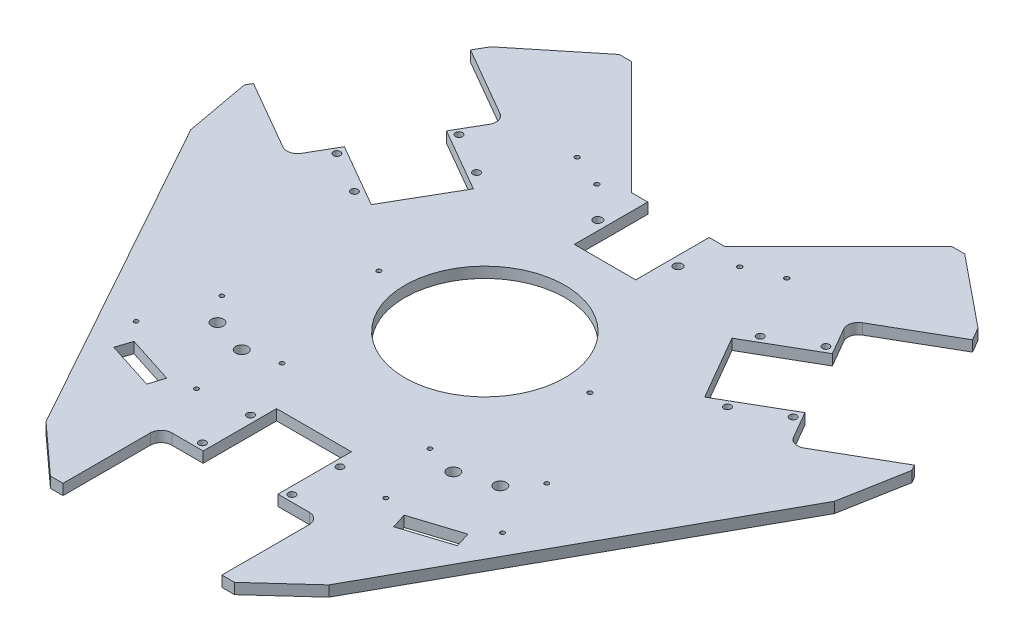
SolidWorks part; units mm, degrees
material "1060 合金"
ref_plane "前视基准面" through (0, 0, 0) normal (0, 0, 1) x (1, 0, 0)
ref_plane "上视基准面" through (0, 0, 0) normal (0, 1, 0) x (1, 0, 0)
ref_plane "右视基准面" through (0, 0, 0) normal (1, 0, 0) x (0, 0, -1)
sketch "草图1" plane through (0, 0, 0) normal (0, 1, 0) x (1, 0, 0)
  line L0 (0, 0) -> (-158.4826, 91.5) construction
  line L1 (0, 0) -> (0, 227.8132) construction
  line L2 (188.2326, 39.9715) -> (128.7326, 143.0285)
  line L3 (188.2326, 39.9715) -> (241.9262, 70.9715)
  line L4 (241.9262, 70.9715) -> (182.4262, 174.0285)
  line L5 (182.4262, 174.0285) -> (128.7326, 143.0285)
  line L6 (0, 0) -> (158.4826, 91.5) construction
  line L7 (-128.7326, 143.0285) -> (-188.2326, 39.9715)
  line L8 (-128.7326, 143.0285) -> (-182.4262, 174.0285)
  line L9 (-182.4262, 174.0285) -> (-241.9262, 70.9715)
  line L10 (-241.9262, 70.9715) -> (-188.2326, 39.9715)
  line L11 (-59.5, -183) -> (59.5, -183)
  line L12 (-59.5, -183) -> (-59.5, -245)
  line L13 (-59.5, -245) -> (59.5, -245)
  line L14 (59.5, -245) -> (59.5, -183)
  line L15 (0, 0) -> (0, -183) construction
  line L16 (-182.4262, 186.924) -> (-250, 69.8827)
  line L17 (-250, 69.8827) -> (-68.9159, -256.4698) construction
  line L18 (-68.9159, -256.4698) -> (68.9159, -256.4698)
  line L19 (250, 69.8827) -> (68.9159, -256.4698) construction
  line L20 (182.4262, 186.924) -> (250, 69.8827)
  line L21 (-129.4169, 230) -> (129.4169, 230)
  line L22 (-250, 69.8827) -> (-241.0069, 20.6982)
  line L23 (-250, -256.4698) -> (250, -256.4698) construction
  line L24 (-250, -256.4698) -> (-250, 243.5302) construction
  line L25 (-250, 243.5302) -> (250, 243.5302) construction
  line L26 (250, -256.4698) -> (250, 243.5302) construction
  line L27 (-250, -256.4698) -> (250, 243.5302) construction
  line L28 (-250, 243.5302) -> (250, -256.4698) construction
  line L29 (-241.0069, 20.6982) -> (-105.8902, -222.8112)
  line L30 (-68.9159, -256.4698) -> (-105.8902, -222.8112)
  line L31 (68.9159, -256.4698) -> (105.8902, -222.8112)
  line L32 (241.0069, 20.6982) -> (105.8902, -222.8112)
  line L33 (250, 69.8827) -> (241.0069, 20.6982)
  line L34 (-182.4262, 186.924) -> (-129.4169, 230)
  line L35 (182.4262, 186.924) -> (129.4169, 230)
  point P21 (0, 0)
  point P24 (0, 0)
  point P29 (0, -6.4698)
  dimension "D1" = 60
  dimension "D2" = 183
  dimension "D3" = 62
  dimension "D4" = 119
  dimension "D6" = 230
  dimension "D7" = 500
  dimension "D8" = 16
  dimension "D9" = 50
  dimension "D5" = 3
extrude "凸台-拉伸1" add sketch "草图1" along normal blind 8
ref_axis "基准轴1" through (0, 0, 0) along (0, 1, 0)
sketch "草图2" plane through (0, 8, 0) normal (0, 1, 0) x (1, 0, 0)
  line L0 (-124.8513, 39.7513) -> (-96.8513, 88.2487)
  line L1 (-182.4262, 174.0285) -> (-241.9262, 70.9715) construction
  line L3 (-96.8513, 88.2487) -> (-144.4826, 115.7487)
  line L4 (-212.1762, 122.5) -> (0, 0) construction
  line L6 (-144.4826, 115.7487) -> (-172.4826, 67.2513)
  line L7 (-172.4826, 67.2513) -> (-124.8513, 39.7513)
  line L8 (-188.2326, 39.9715) -> (-128.7326, 143.0285) construction
  dimension "D1" = 56
  dimension "D2" = 55
extrude "切除-拉伸1" cut sketch "草图2" against normal up to next
hole_wizard "M5 间隙孔1" positions "草图3" profile "草图4" hole size "M5" standard "GB" end condition up to next
sketch "草图3" plane through (0, 8, 0) normal (0, -1, 0) x (-1, 0, 0)
  line L0 (0, 0) -> (212.1762, 122.5) construction
  line L1 (170.9025, 59.9881) -> (139.7256, 41.9881) construction
  line L2 (170.9025, 59.9881) -> (137.4025, 118.0119) construction
  line L3 (139.7256, 41.9881) -> (106.2256, 100.0119) construction
  line L4 (137.4025, 118.0119) -> (106.2256, 100.0119) construction
  line L16 (144.4826, 115.7487) -> (128.7326, 143.0285) construction
  line L18 (182.4262, 174.0285) -> (241.9262, 70.9715) construction
  point P5 (106.2256, 100.0119)
  point P7 (137.4025, 118.0119)
  point P9 (139.7256, 41.9881)
  point P11 (170.9025, 59.9881)
  dimension "D1" = 67
  dimension "D2" = 5
  dimension "D3" = 36
sketch "草图4" plane through (-106.2256, 8, -100.0119) normal (1, 0, 0) x (0, 0, 1)
  line L0 (0, 0) -> (0, 8.001)
  line L1 (0, 8.001) -> (2.65, 8.001)
  line L2 (2.65, 8.001) -> (2.65, 0)
  line L5 (2.65, 0) -> (0, 0)
  line L11 (0, -6.35) -> (0, 107.95) construction
  dimension "通孔孔直径" = 5.3
  dimension "通孔孔深度" = 8.001
sketch "草图11" plane through (0, 8, 0) normal (0, 1, 0) x (1, 0, 0)
  line L0 (182.4262, 174.0285) -> (241.9262, 70.9715)
  line L1 (182.4262, 174.0285) -> (188.0101, 177.2524)
  line L2 (241.9262, 70.9715) -> (247.5101, 74.1953)
  line L3 (188.0101, 177.2524) -> (247.5101, 74.1953)
  line L4 (182.4262, 186.924) -> (250, 69.8827) construction
  line L5 (-59.5, -245) -> (59.5, -245)
  line L6 (-59.5, -245) -> (-59.5, -256.4698)
  line L7 (59.5, -245) -> (59.5, -256.4698)
  line L8 (-59.5, -256.4698) -> (59.5, -256.4698)
  line L9 (-68.9159, -256.4698) -> (68.9159, -256.4698) construction
  line L10 (-241.9262, 70.9715) -> (-182.4262, 174.0285)
  line L11 (-241.9262, 70.9715) -> (-247.5101, 74.1953)
  line L12 (-182.4262, 174.0285) -> (-188.0101, 177.2524)
  line L13 (-247.5101, 74.1953) -> (-188.0101, 177.2524)
  line L14 (-182.4262, 186.924) -> (-250, 69.8827) construction
extrude "切除-拉伸5" cut sketch "草图11" against normal through all
pattern_circular "阵列(圆周)1" count 3 over 360 about axis through (0, 0, 0) along (0, 1, 0) of "切除-拉伸1", "M5 间隙孔1"
sketch "草图5" plane through (0, 8, 0) normal (0, 1, 0) x (1, 0, 0)
  line L0 (-129.4169, 230) -> (129.4169, 230) construction
  line L1 (129.4169, 230) -> (-121.0813, 230) construction
  line L2 (0, 0) -> (0, 310.7708) construction
  line L3 (120, 230) -> (35, 145)
  line L4 (35, 145) -> (-35, 145)
  line L5 (-120, 230) -> (-35, 145)
  line L7 (129.4169, 230) -> (-129.4169, 230) construction
  point P10 (0, 145)
  dimension "D1" = 45
  dimension "D2" = 85
  dimension "D3" = 240
extrude "切除-拉伸2" cut sketch "草图5" against normal through all and the other way through all
sketch "草图7" plane through (0, 8, 0) normal (0, 1, 0) x (1, 0, 0)
  line L1 (0, 0) -> (0, 218.1098) construction
  line L3 (-23, 230) -> (23, 230)
  line L4 (-23, 230) -> (-23, 90)
  line L5 (-23, 90) -> (23, 90)
  line L6 (23, 230) -> (23, 90)
  line L7 (-23, 230) -> (23, 90) construction
  line L8 (-23, 90) -> (23, 230) construction
  point P7 (0, 160)
  dimension "D1" = 90
  dimension "D2" = 46
extrude "切除-拉伸4" cut sketch "草图7" against normal through all
hole_wizard "M6 间隙孔1" positions "草图8" profile "草图9" hole size "M6" standard "GB" end condition up to next
sketch "草图8" plane through (0, 8, 0) normal (0, 1, 0) x (1, 0, 0)
  line L0 (0, 0) -> (0, 212.5269) construction
  line L3 (-23, 90) -> (23, 90) construction
  point P2 (30, 114.64)
  point P4 (-30, 114.64)
  dimension "D1" = 24.64
  dimension "D2" = 60
sketch "草图9" plane through (30, 8, -114.64) normal (1, 0, 0) x (0, 0, 1)
  line L0 (0, 0) -> (0, 8)
  line L1 (0, 8) -> (3.2, 8)
  line L2 (3.2, 8) -> (3.2, 0)
  line L5 (3.2, 0) -> (0, 0)
  line L11 (0, -6.35) -> (0, 107.95) construction
  dimension "通孔孔直径" = 6.4
  dimension "通孔孔深度" = 8
sketch "草图10" plane through (0, 8, 0) normal (0, 1, 0) x (1, 0, 0)
  circle A0 centre (0, 0) radius 60
  dimension "D1" = 120
extrude "中心园孔" cut sketch "草图10" against normal up to next
fillet "圆角1" [suppressed] radius 6
fillet "圆角4" radius 8 6 edges at (-188.2326, 4, -39.9715) (-128.7326, 4, -143.0285) (188.2326, 4, -39.9715) (128.7326, 4, -143.0285) (59.5, 4, 183) (-59.5, 4, 183)
sketch "草图12" plane through (0, 8, 0) normal (0, 1, 0) x (1, 0, 0)
  line L0 (0, -0.36) -> (0, -21.6408) construction
  line L1 (0, 0) -> (0, -183) construction
  line L2 (-79, -0.36) -> (79, -0.36) construction
  circle A0 centre (30, 114.64) radius 3.2 construction
  point P0 (-79, -0.36)
  point P9 (79, -0.36)
  dimension "D1" = 158
  dimension "D2" = 115
hole_wizard "M4 螺纹孔1" positions "草图14" profile "草图13" tap size "M4" standard "GB" end condition through all
sketch "草图14" plane through (0, 8, 0) normal (0, 1, 0) x (1, 0, 0)
  point P0 (-79, -0.36)
  point P3 (79, -0.36)
sketch "草图13" plane through (-79, 8, 0.36) normal (1, 0, 0) x (0, 0, 1)
  line L0 (0, 0) -> (0, 8)
  line L1 (0, 8) -> (1.65, 8)
  line L2 (1.65, 8) -> (1.65, 0)
  line L5 (1.65, 0) -> (0, 0)
  line L11 (0, -6.35) -> (0, 107.95) construction
  dimension "螺纹线主直径" = 3.3
  dimension "通孔螺纹孔钻头深度" = 8
hole_wizard "M3 间隙孔1" positions "草图19" profile "草图20" hole size "M3" standard "GB" end condition up to next
sketch "草图19" plane through (0, 0, 0) normal (0, -1, 0) x (-1, 0, 0)
  line L0 (-88.5156, -85.9468) -> (-122.6418, -192.6211) construction
  line L4 (-70.91, -145.1252) -> (-55.3704, -96.5503)
  line L5 (-70.91, -145.1252) -> (-137.2004, -123.9182)
  line L6 (-137.2004, -123.9182) -> (-121.6608, -75.3433)
  line L7 (-55.3704, -96.5503) -> (-121.6608, -75.3433)
  line L8 (-70.91, -145.1252) -> (-121.6608, -75.3433) construction
  line L9 (-137.2004, -123.9182) -> (-55.3704, -96.5503) construction
  line L14 (0, 0) -> (0, -183) construction
  line L15 (0, 0) -> (0, -140.8647) construction
  line L17 (-241.0069, 20.6982) -> (-105.8902, -222.8112) construction
  line L18 (-79.2338, -102.8802) -> (-105.9024, -94.3486)
  point P7 (-121.6608, -75.3433)
  point P10 (-70.91, -145.1252)
  point P11 (-137.2004, -123.9182)
  point P12 (-55.3704, -96.5503)
  dimension "D1" = 69.6
  dimension "D2" = 51
  dimension "D3" = 17.74
  dimension "D4" = 141.82
  dimension "D5" = 61
  dimension "D6" = 13.3
  dimension "D7" = 28
sketch "草图20" plane through (121.6608, 0, 75.3433) normal (1, 0, 0) x (0, 0, -1)
  line L0 (0, 0) -> (0, 8.001)
  line L1 (0, 8.001) -> (1.6, 8.001)
  line L2 (1.6, 8.001) -> (1.6, 0)
  line L5 (1.6, 0) -> (0, 0)
  line L11 (0, -6.35) -> (0, 107.95) construction
  dimension "通孔孔直径" = 3.2
  dimension "通孔孔深度" = 8.001
hole_wizard "Ø9.0 (9) 直径孔1" positions "草图23" profile "草图22" hole size "Ø9.0" standard "GB" end condition through all
sketch "草图23" plane through (0, 0, 0) normal (0, -1, 0) x (-1, 0, 0)
  point P0 (-105.9024, -94.3486)
  point P3 (-79.2338, -102.8802)
sketch "草图22" plane through (105.9024, 0, 94.3486) normal (1, 0, 0) x (0, 0, -1)
  line L0 (0, 0) -> (0, 8)
  line L1 (0, 8) -> (4.5, 8)
  line L2 (4.5, 8) -> (4.5, 0)
  line L5 (4.5, 0) -> (0, 0)
  line L11 (0, -6.35) -> (0, 107.95) construction
  dimension "通孔孔直径" = 9
  dimension "通孔孔深度" = 8
sketch "草图21" plane through (0, 0, 0) normal (0, -1, 0) x (1, 0, 0)
  line L1 (88.8533, 149.3593) -> (92.5097, 160.7887)
  line L2 (88.8533, 149.3593) -> (125.0464, 137.7807)
  line L3 (125.0464, 137.7807) -> (128.7028, 149.2101)
  line L4 (92.5097, 160.7887) -> (128.7028, 149.2101)
  line L5 (88.8533, 149.3593) -> (128.7028, 149.2101) construction
  line L6 (125.0464, 137.7807) -> (92.5097, 160.7887) construction
  line L7 (137.2004, 123.9182) -> (70.91, 145.1252) construction
  line L8 (104.0552, 134.5217) -> (114.5314, 167.2691) construction
  point P0 (108.778, 149.2847)
  dimension "D1" = 38
  dimension "D2" = 12
  dimension "D3" = 9.5
extrude "切除-拉伸6" cut sketch "草图21" against normal blind 10
sketch "草图28" plane through (0, 0, 0) normal (0, -1, 0) x (-1, 0, 0)
  point P0 (53.5172, 137.3863)
  point P1 (78.5089, 147.6045)
hole_wizard "M3 间隙孔3" positions "草图30" profile "草图29" hole size "M3" standard "GB" end condition through all
sketch "草图30" plane through (0, 0, 0) normal (0, -1, 0) x (-1, 0, 0)
  point P0 (53.5172, 137.3863)
  point P3 (78.5089, 147.6045)
sketch "草图29" plane through (-53.5172, 0, -137.3863) normal (1, 0, 0) x (0, 0, -1)
  line L0 (0, 0) -> (0, 8)
  line L1 (0, 8) -> (1.7, 8)
  line L2 (1.7, 8) -> (1.7, 0)
  line L5 (1.7, 0) -> (0, 0)
  line L11 (0, -6.35) -> (0, 107.95) construction
  dimension "通孔孔直径" = 3.4
  dimension "通孔孔深度" = 8
mirror "镜向1" about plane through (0, 0, 0) normal (1, 0, 0) of "M3 间隙孔3", "切除-拉伸6", "M3 间隙孔1", "Ø9.0 (9) 直径孔1"
